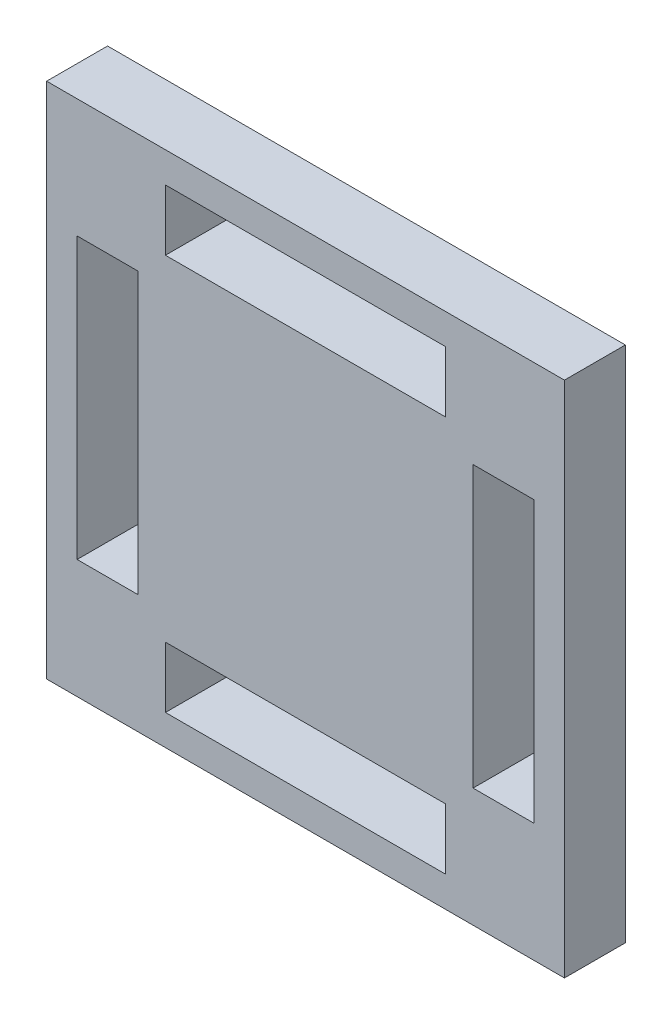
SolidWorks part; units mm, degrees
ref_plane "正面" through (0, 0, 0) normal (0, 0, 1) x (1, 0, 0)
ref_plane "平面" through (0, 0, 0) normal (0, 1, 0) x (1, 0, 0)
ref_plane "右側面" through (0, 0, 0) normal (1, 0, 0) x (0, 0, -1)
sketch "ｽｹｯﾁ1" plane through (0, 0, 0) normal (0, 0, 1) x (1, 0, 0)
  line L1 (-37.5, -37.5) -> (37.5, -37.5)
  line L2 (-37.5, -37.5) -> (-37.5, 37.5)
  line L3 (-37.5, 37.5) -> (37.5, 37.5)
  line L4 (37.5, -37.5) -> (37.5, 37.5)
  line L5 (-37.5, -37.5) -> (37.5, 37.5) construction
  line L6 (-37.5, 37.5) -> (37.5, -37.5) construction
  point P0 (0, 0)
  dimension "D1" = 75
  dimension "D2" = 75
extrude "ﾎﾞｽ - 押し出し1" add sketch "ｽｹｯﾁ1" along normal blind 15
sketch "ｽｹｯﾁ2" plane through (0, 0, 0) normal (0, 0, -1) x (-1, 0, 0)
  line L0 (-37.5, 37.5) -> (37.5, -37.5) construction
  line L1 (-37.5, -37.5) -> (37.5, 37.5) construction
  line L2 (0, -37.5) -> (0, 37.5) construction
  line L3 (37.5, -37.5) -> (-37.5, -37.5) construction
  line L4 (-37.5, 37.5) -> (37.5, 37.5) construction
  line L5 (-37.5, 0) -> (37.5, 0) construction
  line L6 (-37.5, -37.5) -> (-37.5, 37.5) construction
  line L7 (37.5, 37.5) -> (37.5, -37.5) construction
  line L9 (27.5, -27.5) -> (-27.5, -27.5) construction
  line L10 (27.5, -27.5) -> (27.5, 27.5) construction
  line L11 (27.5, 27.5) -> (-27.5, 27.5) construction
  line L12 (-27.5, -27.5) -> (-27.5, 27.5) construction
  line L13 (27.5, -27.5) -> (-27.5, 27.5) construction
  line L14 (27.5, 27.5) -> (-27.5, -27.5) construction
  circle A0 centre (-17.136, -23.5) radius 4
  circle A1 centre (17.136, -23.5) radius 4
  circle A2 centre (-23.5, 17.136) radius 4
  circle A3 centre (-23.5, -17.136) radius 4
  circle A4 centre (23.5, -17.136) radius 4
  circle A5 centre (23.5, 17.136) radius 4
  circle A6 centre (17.136, 23.5) radius 4
  circle A7 centre (-17.136, 23.5) radius 4
  point P20 (0, 0)
  dimension "D2" = 8
  dimension "D1" = 10
  dimension "D3" = 4.5
  dimension "D4" = 4
extrude "ｶｯﾄ - 押し出し1" [suppressed] cut sketch "ｽｹｯﾁ2" against normal blind 2.8
sketch "ｽｹｯﾁ3" plane through (0, 0, 0) normal (0, 0, -1) x (-1, 0, 0)
  line L0 (-37.5, 37.5) -> (37.5, -37.5) construction
  line L1 (37.5, 37.5) -> (-37.5, -37.5) construction
  line L2 (-37.5, 0) -> (37.5, 0) construction
  line L3 (-37.5, -37.5) -> (-37.5, 37.5) construction
  line L4 (37.5, 37.5) -> (37.5, -37.5) construction
  line L5 (0, 37.5) -> (0, -37.5) construction
  line L6 (-37.5, 37.5) -> (37.5, 37.5) construction
  line L7 (37.5, -37.5) -> (-37.5, -37.5) construction
  line L9 (-32.5, -32.5) -> (32.5, -32.5) construction
  line L10 (-32.5, -32.5) -> (-32.5, 32.5) construction
  line L11 (-32.5, 32.5) -> (32.5, 32.5) construction
  line L12 (32.5, -32.5) -> (32.5, 32.5) construction
  line L13 (-32.5, -32.5) -> (32.5, 32.5) construction
  line L14 (-32.5, 32.5) -> (32.5, -32.5) construction
  circle A0 centre (-1.5, -30.5) radius 0.75
  point P20 (0, 0)
  dimension "D2" = 1.5
  dimension "D3" = 2
  dimension "D1" = 5
  dimension "D4" = 1.5
extrude "ｶｯﾄ - 押し出し2" [suppressed] cut sketch "ｽｹｯﾁ3" against normal through all
sketch "ｽｹｯﾁ4" plane through (0, 0, 15) normal (0, 0, 1) x (1, 0, 0)
  line L0 (5.395, -24.25) -> (0.145, -24.25) construction
  line L1 (5.495, -21.25) -> (0.045, -21.25)
  line L2 (5.495, -21.25) -> (5.495, -27.75)
  line L3 (5.495, -27.75) -> (0.045, -27.75)
  line L4 (0.045, -21.25) -> (0.045, -27.75)
  line L5 (5.395, -26.75) -> (5.395, -24.25) construction
  line L6 (0.145, -26.75) -> (5.395, -26.75) construction
  line L7 (0.145, -24.25) -> (0.145, -26.75) construction
  dimension "D1" = 3
  dimension "D2" = 0.1
  dimension "D3" = 1
  dimension "D4" = 0.1
extrude "ｶｯﾄ - 押し出し5" [suppressed] cut sketch "ｽｹｯﾁ4" against normal up to surface (7 mm away)
sketch "ｽｹｯﾁ5" [suppressed] plane through (0, 0, 2.8) normal (0, 0, -1) x (-1, 0, 0)
  text T0 "<b>+</b>"
  text T1 "<b>_</b>"
sketch "ｽｹｯﾁ6" plane through (0, 0, 0) normal (0, 0, -1) x (-1, 0, 0)
  circle A0 centre (0, 0) radius 17.5
  dimension "D1" = 35
extrude "ｶｯﾄ - 押し出し7" cut sketch "ｽｹｯﾁ6" against normal blind 1
sketch "ｽｹｯﾁ7" plane through (0, 0, 0) normal (0, 0, -1) x (-1, 0, 0)
  line L1 (-37.5, 37.5) -> (37.5, 37.5)
  line L2 (-37.5, 37.5) -> (-37.5, -37.5)
  line L3 (-37.5, -37.5) -> (37.5, -37.5)
  line L4 (37.5, 37.5) -> (37.5, -37.5)
  line L9 (27.5, -27.5) -> (-27.5, -27.5)
  line L10 (27.5, -27.5) -> (27.5, 27.5)
  line L11 (27.5, 27.5) -> (-27.5, 27.5)
  line L12 (-27.5, -27.5) -> (-27.5, 27.5)
  line L13 (27.5, -27.5) -> (-27.5, 27.5) construction
  line L14 (27.5, 27.5) -> (-27.5, -27.5) construction
  point P6 (0, 0)
  dimension "D1" = 10
extrude "ｶｯﾄ - 押し出し8" cut sketch "ｽｹｯﾁ7" against normal blind 5
extrude "ｶｯﾄ - 押し出し6" [suppressed] cut sketch "ｽｹｯﾁ5" against normal blind 1
ref_plane "平面1" through (0, 0, 0) normal (1, 0, 0) x (0, 0, -1)
ref_plane "平面2" through (0, 0, 0) normal (0.7071, 0.7071, 0) x (0.7071, -0.7071, 0)
ref_plane "平面3" through (0, 0, 0) normal (0.7071, -0.7071, 0) x (-0.7071, -0.7071, 0)
ref_axis "軸1" through (0, 0, 5.25) along (0, 0, -1)
pattern_circular "円形ﾊﾟﾀｰﾝ1" [suppressed] count 4 over 360 about axis through (0, 0, 5.25) along (0, 0, -1) of bodies 106
sketch "ｽｹｯﾁ8" plane through (0, 0, 5) normal (0, 0, -1) x (-1, 0, 0)
  line L0 (-37.5, 37.5) -> (-37.5, -37.5) construction
  line L1 (-37.5, 23) -> (-27.5, 23)
  line L2 (-37.5, 23) -> (-37.5, -23)
  line L3 (-37.5, -23) -> (-27.5, -23)
  line L4 (-27.5, 23) -> (-27.5, -23)
  line L5 (-27.5, 27.5) -> (-27.5, -27.5) construction
  line L6 (27.5, -27.5) -> (27.5, 27.5) construction
  line L7 (27.5, 23) -> (37.5, 23)
  line L8 (27.5, 23) -> (27.5, -23)
  line L9 (27.5, -23) -> (37.5, -23)
  line L10 (37.5, 23) -> (37.5, -23)
  line L11 (37.5, -37.5) -> (37.5, 37.5) construction
  line L12 (0, 0) -> (52.1583, 0) construction
  line L13 (-27.5, -27.5) -> (27.5, -27.5) construction
  line L14 (-23, -27.5) -> (23, -27.5)
  line L15 (-23, -27.5) -> (-23, -37.5)
  line L16 (-23, -37.5) -> (23, -37.5)
  line L17 (23, -27.5) -> (23, -37.5)
  line L18 (-37.5, -37.5) -> (37.5, -37.5) construction
  line L19 (27.5, 27.5) -> (-27.5, 27.5) construction
  line L20 (-23, 27.5) -> (23, 27.5)
  line L21 (-23, 27.5) -> (-23, 37.5)
  line L22 (-23, 37.5) -> (23, 37.5)
  line L23 (23, 27.5) -> (23, 37.5)
  line L24 (37.5, 37.5) -> (-37.5, 37.5) construction
  line L25 (0, 0) -> (0, -27.5) construction
  point P37 (0, 27.5)
  point P39 (23.8333, -37.5)
  point P40 (0, -27.5)
  dimension "D1" = 46
  dimension "D2" = 46
extrude "ｶｯﾄ - 押し出し9" cut sketch "ｽｹｯﾁ8" against normal through all
sketch "ｽｹｯﾁ9" plane through (0, 0, 5) normal (0, 0, -1) x (-1, 0, 0)
  line L1 (-37.5, -37.5) -> (37.5, -37.5)
  line L2 (-37.5, -37.5) -> (-37.5, 37.5)
  line L3 (-37.5, 37.5) -> (37.5, 37.5)
  line L4 (37.5, -37.5) -> (37.5, 37.5)
  line L5 (-37.5, -37.5) -> (37.5, 37.5) construction
  line L6 (-37.5, 37.5) -> (37.5, -37.5) construction
  line L7 (-42.5, -42.5) -> (42.5, -42.5)
  line L8 (-42.5, -42.5) -> (-42.5, 42.5)
  line L9 (-42.5, 42.5) -> (42.5, 42.5)
  line L10 (42.5, -42.5) -> (42.5, 42.5)
  line L11 (-42.5, -42.5) -> (42.5, 42.5) construction
  line L12 (-42.5, 42.5) -> (42.5, -42.5) construction
  point P0 (0, 0)
  point P7 (0, 0)
  dimension "D1" = 5
extrude "ﾎﾞｽ - 押し出し2" add sketch "ｽｹｯﾁ9" against normal up to surface (10 mm away) up to face at (0, 0, 15)
equation "\"D2@ｽｹｯﾁ8\"=\"D1@ｽｹｯﾁ8\""
